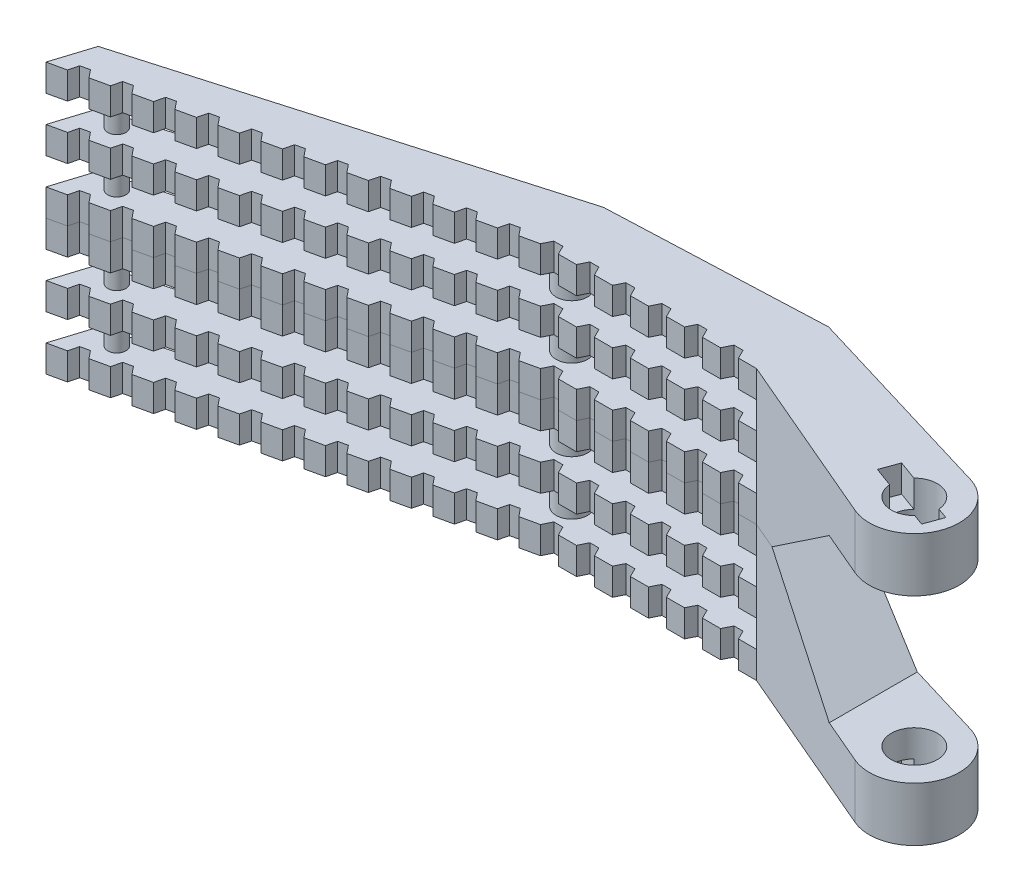
SolidWorks part; units mm, degrees
ref_plane "前视基准面" through (0, 0, 0) normal (0, 0, 1) x (1, 0, 0)
ref_plane "上视基准面" through (0, 0, 0) normal (0, 1, 0) x (1, 0, 0)
ref_plane "右视基准面" through (0, 0, 0) normal (1, 0, 0) x (0, 0, -1)
other "Configuration Table"
ref_axis "基准轴1" through (0, -20.495, 0) along (0, 1, 0)
sketch "草图1" plane through (0, 0, 0) normal (0, 1, 0) x (1, 0, 0)
  line L10 (0, 0) -> (0, -6.4) construction
  line L11 (0, -6.4) -> (-90, -6.4) construction
  line L27 (-1.9651, -4.5977) -> (-21.0954, 3.5788)
  line L29 (-45.0954, 3.5788) -> (-90, -6.4) construction
  line L30 (-90, -6.4) -> (-88.6133, -1.9943)
  line L31 (-88.6133, -1.9943) -> (-45.0954, 10.5788)
  line L32 (-45.0954, 10.5788) -> (-21.0954, 11.5788)
  line L33 (-21.0954, 11.5788) -> (1.4426, 4.7874)
  line L34 (-87.7765, -4.8815) -> (-86.8003, -4.6646)
  line L35 (-86.8003, -4.6646) -> (-86.0953, -5.5323)
  line L36 (-87.7765, -4.8815) -> (-88.0476, -5.9661)
  line L37 (-87.2884, -4.773) -> (-87.0714, -5.7492) construction
  line L38 (-86.0953, -5.5323) -> (-84.1429, -5.0984)
  line L39 (-88.0476, -5.9661) -> (-90, -6.4)
  line L40 (-83.8717, -4.0138) -> (-84.1429, -5.0984)
  line L41 (-83.8717, -4.0138) -> (-82.8955, -3.7968)
  line L42 (-82.8955, -3.7968) -> (-82.1905, -4.6646)
  line L43 (-82.1905, -4.6646) -> (-80.2381, -4.2307)
  line L44 (-79.967, -3.146) -> (-80.2381, -4.2307)
  line L45 (-79.967, -3.146) -> (-78.9908, -2.9291)
  line L46 (-78.9908, -2.9291) -> (-78.2858, -3.7968)
  line L47 (-78.2858, -3.7968) -> (-76.3334, -3.363)
  line L48 (-76.0622, -2.2783) -> (-76.3334, -3.363)
  line L49 (-76.0622, -2.2783) -> (-75.086, -2.0614)
  line L50 (-75.086, -2.0614) -> (-74.381, -2.9291)
  line L51 (-74.381, -2.9291) -> (-72.4286, -2.4953)
  line L52 (-72.1575, -1.4106) -> (-72.4286, -2.4953)
  line L53 (-72.1575, -1.4106) -> (-71.1813, -1.1937)
  line L54 (-71.1813, -1.1937) -> (-70.4763, -2.0614)
  line L55 (-70.4763, -2.0614) -> (-68.5239, -1.6275)
  line L56 (-68.2527, -0.5429) -> (-68.5239, -1.6275)
  line L57 (-68.2527, -0.5429) -> (-67.2765, -0.3259)
  line L58 (-67.2765, -0.3259) -> (-66.5715, -1.1937)
  line L59 (-66.5715, -1.1937) -> (-64.6191, -0.7598)
  line L60 (-64.348, 0.3248) -> (-64.6191, -0.7598)
  line L61 (-64.348, 0.3248) -> (-63.3718, 0.5418)
  line L62 (-63.3718, 0.5418) -> (-62.6668, -0.3259)
  line L63 (-62.6668, -0.3259) -> (-60.7144, 0.1079)
  line L64 (-60.4432, 1.1926) -> (-60.7144, 0.1079)
  line L65 (-60.4432, 1.1926) -> (-59.467, 1.4095)
  line L66 (-59.467, 1.4095) -> (-58.762, 0.5418)
  line L67 (-58.762, 0.5418) -> (-56.8096, 0.9756)
  line L68 (-56.5385, 2.0603) -> (-56.8096, 0.9756)
  line L69 (-56.5385, 2.0603) -> (-55.5623, 2.2772)
  line L70 (-55.5623, 2.2772) -> (-54.8573, 1.4095)
  line L71 (-54.8573, 1.4095) -> (-52.9049, 1.8434)
  line L72 (-52.6337, 2.928) -> (-52.9049, 1.8434)
  line L73 (-52.6337, 2.928) -> (-51.6575, 3.1449)
  line L74 (-51.6575, 3.1449) -> (-50.9525, 2.2772)
  line L75 (-50.9525, 2.2772) -> (-49.0001, 2.7111)
  line L76 (-48.729, 3.7957) -> (-49.0001, 2.7111)
  line L77 (-48.729, 3.7957) -> (-47.7528, 4.0127)
  line L78 (-47.7528, 4.0127) -> (-47.0478, 3.1449)
  line L79 (-47.0478, 3.1449) -> (-45.0954, 3.5788)
  line L80 (-43.0954, 3.5788) -> (-41.0954, 3.5788)
  line L81 (-45.0954, 3.5788) -> (-44.5954, 4.5788)
  line L82 (-44.5954, 4.5788) -> (-43.5954, 4.5788)
  line L83 (-43.5954, 4.5788) -> (-43.0954, 3.5788)
  line L84 (-45.0954, 3.5788) -> (-43.0954, 3.5788) construction
  line L85 (-23.3489, 3.5788) -> (-29.0874, 3.5788) construction
  line L86 (-41.0954, 3.5788) -> (-40.5954, 4.5788)
  line L87 (-40.5954, 4.5788) -> (-39.5954, 4.5788)
  line L88 (-39.5954, 4.5788) -> (-39.0954, 3.5788)
  line L89 (-39.0954, 3.5788) -> (-37.0954, 3.5788)
  line L90 (-41.0954, 3.5788) -> (-39.0954, 3.5788) construction
  line L91 (-37.0954, 3.5788) -> (-36.5954, 4.5788)
  line L92 (-36.5954, 4.5788) -> (-35.5954, 4.5788)
  line L93 (-35.5954, 4.5788) -> (-35.0954, 3.5788)
  line L94 (-35.0954, 3.5788) -> (-33.0954, 3.5788)
  line L95 (-37.0954, 3.5788) -> (-35.0954, 3.5788) construction
  line L96 (-33.0954, 3.5788) -> (-32.5954, 4.5788)
  line L97 (-32.5954, 4.5788) -> (-31.5954, 4.5788)
  line L98 (-31.5954, 4.5788) -> (-31.0954, 3.5788)
  line L99 (-31.0954, 3.5788) -> (-29.0954, 3.5788)
  line L100 (-33.0954, 3.5788) -> (-31.0954, 3.5788) construction
  line L101 (-29.0954, 3.5788) -> (-28.5954, 4.5788)
  line L102 (-28.5954, 4.5788) -> (-27.5954, 4.5788)
  line L103 (-27.5954, 4.5788) -> (-27.0954, 3.5788)
  line L104 (-27.0954, 3.5788) -> (-25.0954, 3.5788)
  line L105 (-29.0954, 3.5788) -> (-27.0954, 3.5788) construction
  line L106 (-25.0954, 3.5788) -> (-24.5954, 4.5788)
  line L107 (-24.5954, 4.5788) -> (-23.5954, 4.5788)
  line L108 (-23.5954, 4.5788) -> (-23.0954, 3.5788)
  line L109 (-23.0954, 3.5788) -> (-21.0954, 3.5788)
  line L110 (-25.0954, 3.5788) -> (-23.0954, 3.5788) construction
  line L111 (-21.0954, 11.5788) -> (-21.0954, 3.5788) construction
  line L112 (-90, -6.4) -> (0, 0) construction
  arc A0 (1.4426, 4.7874) -> (-1.9651, -4.5977) centre (0, 0) cw
  point P38 (-44.0954, 4.5788)
  point P43 (-44.0954, 3.5788)
  dimension "D4" = 7
  dimension "D3" = 5
  dimension "D1" = 6.4
  dimension "D2" = 90
  dimension "D6" = 2
  dimension "D7" = 8
  dimension "D8" = 2
  dimension "D9" = 60
  dimension "D10" = 4
  dimension "D11" = 1
  dimension "D12" = 1
  dimension "D13" = 2
  dimension "D14" = 2
  dimension "D15" = 2
  dimension "D17" = 1
  dimension "D18" = 1
  dimension "D19" = 6
  dimension "D16" = 11
extrude "凸台-拉伸2" add sketch "草图1" along normal blind 15 and the other way blind 15
sketch "草图10" plane through (0, 0, 0) normal (0, 0, 1) x (1, 0, 0)
  line L0 (5, 9) -> (-7, 9)
  line L1 (5, -15) -> (5, 15) construction
  line L4 (55, 0) -> (-55, 0) construction
  line L8 (5, 15) -> (-1.9651, 15) construction
  line L12 (-18.0954, 0) -> (19.8896, 0) construction
  line L14 (-18.0954, 0) -> (-7, 9)
  line L15 (5, 9) -> (5, -9)
  line L16 (5, -15) -> (5, 15) construction
  line L17 (-18.0954, 0) -> (-7, -9)
  line L18 (5, -9) -> (-7, -9)
  line L19 (-21.0954, -15) -> (-21.0954, 15) construction
  point P18 (5, 0)
  point P26 (5, 0)
  dimension "D1" = 6
  dimension "D2" = 3
  dimension "D3" = 12
extrude "切除-拉伸7" cut sketch "草图10" against normal through all and the other way through all
sketch "草图3" plane through (0, 0, 0) normal (0, 0, 1) x (1, 0, 0)
  line L0 (-21.0954, 15) -> (-1.9651, 15) construction
  line L1 (-121.0954, 12) -> (-21.0954, 12)
  line L2 (-121.0954, 12) -> (-121.0954, 9)
  line L3 (-121.0954, 9) -> (-21.0954, 9)
  line L4 (-21.0954, 12) -> (-21.0954, 9)
  line L5 (-21.0954, 38.654) -> (-21.0954, -13.8848) construction
  line L8 (-21.0954, -15) -> (-21.0954, 15) construction
  line L10 (-121.0954, 6) -> (-21.0954, 6)
  line L11 (-121.0954, 6) -> (-121.0954, 3)
  line L12 (-121.0954, 3) -> (-21.0954, 3)
  line L13 (-21.0954, 6) -> (-21.0954, 3)
  line L14 (55, 0) -> (-55, 0) construction
  line L15 (0, 0) -> (34.3491, 0) construction
  line L16 (-21.0954, -6) -> (-21.0954, -3)
  line L17 (-121.0954, -3) -> (-21.0954, -3)
  line L18 (-121.0954, -6) -> (-121.0954, -3)
  line L19 (-121.0954, -6) -> (-21.0954, -6)
  line L20 (-21.0954, -12) -> (-21.0954, -9)
  line L21 (-121.0954, -9) -> (-21.0954, -9)
  line L22 (-121.0954, -12) -> (-121.0954, -9)
  line L23 (-121.0954, -12) -> (-21.0954, -12)
  dimension "D1" = 3
  dimension "D2" = 100
  dimension "D3" = 3
  dimension "D5" = 3
  dimension "D6" = 3
extrude "切除-拉伸8" cut sketch "草图3" against normal through all and the other way through all
sketch "草图4" plane through (0, -15, 0) normal (0, -1, 0) x (1, 0, 0)
  line L2 (-45.0954, -3.5788) -> (-45.0954, -10.5788) construction
  line L3 (-21.0954, -3.5788) -> (-21.0954, -11.5788) construction
  line L4 (-86.2115, 1.3004) -> (-85.7952, 2.7414) construction
  line L5 (-45.0954, -10.5788) -> (-88.6133, 1.9943) construction
  circle A3 centre (-45.0954, -7.0788) radius 1.75
  circle A4 centre (-85.7952, 2.7414) radius 1
  point P27 (-45.0954, -7.0788)
  dimension "D1" = 2.5
  dimension "D2" = 3.5
  dimension "D3" = 2
  dimension "D4" = 1.5
extrude "凸台-拉伸3" add sketch "草图4" against normal up to surface (30 mm away) up to face at (-54.0883, 15, -0.9738)
sketch "草图5" plane through (0, -15, 0) normal (0, -1, 0) x (1, 0, 0)
  circle A0 centre (0, 0) radius 2.55
  dimension "D1" = 5.1
extrude "切除-拉伸2" cut sketch "草图5" against normal through all
sketch "草图8" plane through (0, -15, 0) normal (0, -1, 0) x (1, 0, 0)
  line L0 (0, 0) -> (-4.3238, -1.57) construction
  line L1 (1.4426, -4.7874) -> (-21.0954, -11.5788) construction
  line L2 (-21.0954, -3.5788) -> (-1.9651, 4.5977) construction
  line L3 (-4.6822, -0.583) -> (-3.9654, -2.5569)
  line L7 (-4.6822, -0.583) -> (3.0255, 2.2156)
  line L8 (-3.9654, -2.5569) -> (3.7422, 0.2417)
  line L9 (0, 0) -> (3.3838, 1.2287) construction
  line L10 (3.7422, 0.2417) -> (3.0255, 2.2156)
  point P9 (-4.3238, -1.57)
  point P10 (3.3838, 1.2287)
  dimension "D1" = 4.6
  dimension "D2" = 2.1
  dimension "D3" = 3.6
extrude "切除-拉伸5" cut sketch "草图8" against normal blind 3
mirror "镜向1" about plane through (0, 0, 0) normal (0, 1, 0) of "切除-拉伸5"
sketch "草图12" plane through (0, 0, 0) normal (0, 0, 1) x (1, 0, 0)
  line L0 (-94.8058, 0) -> (15.6219, 0)
  line L1 (9.8883, 0) -> (-9.8883, 0) construction
split "分割1" trim tools "草图12" bodies to split 123 resulting bodies 124 125
